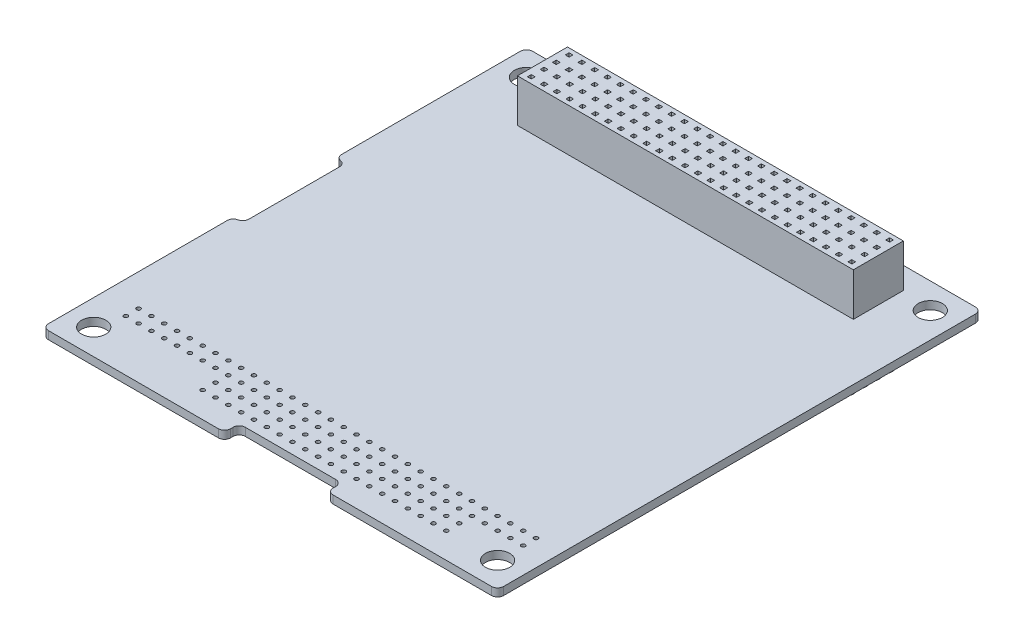
SolidWorks part; units mm, degrees
ref_plane "Front Plane" through (0, 0, 0) normal (0, 0, 1) x (1, 0, 0)
ref_plane "Top Plane" through (0, 0, 0) normal (0, 1, 0) x (1, 0, 0)
ref_plane "Right Plane" through (0, 0, 0) normal (1, 0, 0) x (0, 0, -1)
sketch "Sketch1" plane through (0, 0, 0) normal (0, 1, 0) x (1, 0, 0)
  line L1 (-45.085, -47.945) -> (45.085, -47.945)
  line L2 (-45.085, -47.945) -> (-45.085, 47.945)
  line L3 (-45.085, 47.945) -> (45.085, 47.945)
  line L4 (45.085, -47.945) -> (45.085, 47.945)
  line L5 (-45.085, -47.945) -> (45.085, 47.945) construction
  line L6 (-45.085, 47.945) -> (45.085, -47.945) construction
  point P0 (0, 0)
  dimension "D1" = 95.89
  dimension "D2" = 90.17
extrude "Boss-Extrude1" add sketch "Sketch1" along normal blind 1.57
sketch "Sketch2" plane through (0, 1.57, 0) normal (0, 1, 0) x (1, 0, 0)
  line L0 (-45.085, 47.945) -> (-9.015, 47.945) construction
  line L1 (45.085, 47.945) -> (-45.085, 47.945) construction
  line L2 (-45.085, -47.945) -> (-45.085, -10.135) construction
  line L3 (-9.015, 47.945) -> (11.305, 47.945)
  line L4 (-9.015, 47.945) -> (-9.015, 45.015)
  line L5 (-9.015, 45.015) -> (11.305, 45.015)
  line L6 (11.305, 47.945) -> (11.305, 45.015)
  line L7 (-45.085, 47.945) -> (-45.085, -47.945) construction
  line L8 (-45.085, -47.945) -> (-9.015, -47.945) construction
  line L9 (-45.085, -10.135) -> (-43.165, -10.135)
  line L10 (-45.085, -10.135) -> (-45.085, 10.135)
  line L11 (-45.085, 10.135) -> (-43.165, 10.135)
  line L12 (-43.165, -10.135) -> (-43.165, 10.135)
  line L13 (-45.085, -47.945) -> (45.085, -47.945) construction
  line L15 (-9.015, -47.945) -> (11.305, -47.945)
  line L16 (-9.015, -47.945) -> (-9.015, -45.025)
  line L17 (-9.015, -45.025) -> (11.305, -45.025)
  line L18 (11.305, -47.945) -> (11.305, -45.025)
  dimension "D1" = 36.07
  dimension "D2" = 20.32
  dimension "D3" = 2.93
  dimension "D4" = 37.81
  dimension "D5" = 20.27
  dimension "D6" = 1.92
  dimension "D7" = 2.92
extrude "Cut-Extrude1" cut sketch "Sketch2" against normal blind 1.57
sketch "Sketch3" plane through (0, 1.57, 0) normal (0, 1, 0) x (1, 0, 0)
  line L0 (-45.085, -47.945) -> (-40.005, -47.945) construction
  line L1 (-45.085, -47.945) -> (-9.015, -47.945) construction
  line L2 (-40.005, -47.945) -> (-40.005, -42.865) construction
  line L3 (45.085, -47.945) -> (40.005, -47.945) construction
  line L4 (11.305, -47.945) -> (45.085, -47.945) construction
  line L5 (40.005, -47.945) -> (40.005, -42.865) construction
  line L6 (-45.085, 47.945) -> (-40.005, 47.945) construction
  line L7 (-9.015, 47.945) -> (-45.085, 47.945) construction
  line L8 (-40.005, 47.945) -> (-40.005, 42.865) construction
  circle A0 centre (-40.005, -42.865) radius 2.4
  circle A1 centre (40.005, -42.865) radius 2.4
  circle A2 centre (-40.005, 42.865) radius 2.4
  circle A3 centre (40.005, 42.865) radius 2.4
  dimension "D3" = 4.8
  dimension "D6" = 5.08
  dimension "D4" = 5.08
  dimension "D5" = 4.8
  dimension "D7" = 4.8
  dimension "D8" = 4.8
  dimension "D1" = 5.08
  dimension "D2" = 5.08
extrude "Cut-Extrude2" cut sketch "Sketch3" against normal blind 1.57
sketch "Sketch4" plane through (0, 1.57, 0) normal (0, 1, 0) x (1, 0, 0)
  line L0 (-45.085, 47.945) -> (-45.085, 35.245) construction
  line L1 (-45.085, 47.945) -> (-45.085, 10.135) construction
  line L2 (-45.085, 35.245) -> (-31.115, 35.245) construction
  line L3 (-31.115, 35.245) -> (-32.639, 35.245)
  line L4 (-32.639, 35.245) -> (-32.639, 33.721) construction
  line L6 (-32.639, 33.721) -> (33.909, 33.721)
  line L7 (-32.639, 33.721) -> (-32.639, 43.627)
  line L8 (-32.639, 43.627) -> (33.909, 43.627)
  line L9 (33.909, 33.721) -> (33.909, 43.627)
  dimension "D1" = 12.7
  dimension "D2" = 13.97
  dimension "D3" = 1.524
  dimension "D4" = 1.524
  dimension "D5" = 9.906
  dimension "D6" = 66.548
extrude "Boss-Extrude3" add sketch "Sketch4" along normal blind 8.509 contours L6 L9 L8 L7 region at (0.635, 1.57, -38.674)
fillet "Fillet7" radius 1.2 1 edges at (-9.015, 0.785, 45.025)
fillet "Fillet8" radius 1.2 1 edges at (-9.015, 0.785, 47.945)
fillet "Fillet9" radius 1.2 2 edges at (11.305, 0.785, 47.945) (11.305, 0.785, 45.025)
fillet "Fillet10" radius 1.2 1 edges at (45.085, 0.785, 47.945)
fillet "Fillet11" radius 1.2 1 edges at (45.085, 0.785, -47.945)
fillet "Fillet12" radius 1.2 2 edges at (11.305, 0.785, -45.015) (11.305, 0.785, -47.945)
fillet "Fillet13" radius 1.2 2 edges at (-9.015, 0.785, -47.945) (-9.015, 0.785, -45.015)
fillet "Fillet14" radius 1.2 1 edges at (-45.085, 0.785, -47.945)
fillet "Fillet17" radius 1.2 1 edges at (-45.085, 0.785, -10.135)
fillet "Fillet18" radius 1.2 1 edges at (-43.165, 0.785, -10.135)
fillet "Fillet19" radius 1.2 1 edges at (-45.085, 0.785, 10.135)
fillet "Fillet20" radius 1.2 1 edges at (-43.165, 0.785, 10.135)
fillet "Fillet21" radius 1.2 1 edges at (-45.085, 0.785, 47.945)
sketch "Sketch7" plane through (0, 10.079, 0) normal (0, 1, 0) x (1, 0, 0)
  line L0 (-32.639, 33.721) -> (-31.115, 33.721) construction
  line L1 (-32.639, 33.721) -> (33.909, 33.721) construction
  line L2 (-31.115, 33.721) -> (-31.115, 34.9275) construction
  line L3 (-28.956, 34.5465) -> (-28.194, 34.5465)
  line L4 (-31.496, 34.5465) -> (-30.734, 34.5465)
  line L5 (-31.496, 34.5465) -> (-31.496, 35.3085)
  line L6 (-31.496, 35.3085) -> (-30.734, 35.3085)
  line L7 (-30.734, 34.5465) -> (-30.734, 35.3085)
  line L8 (-31.496, 34.5465) -> (-30.734, 35.3085) construction
  line L9 (-31.496, 35.3085) -> (-30.734, 34.5465) construction
  line L10 (-28.194, 34.5465) -> (-28.194, 35.3085)
  line L11 (-28.956, 35.3085) -> (-28.194, 35.3085)
  line L12 (-28.956, 34.5465) -> (-28.956, 35.3085)
  line L13 (-26.416, 34.5465) -> (-25.654, 34.5465)
  line L14 (-25.654, 34.5465) -> (-25.654, 35.3085)
  line L15 (-26.416, 35.3085) -> (-25.654, 35.3085)
  line L16 (-26.416, 34.5465) -> (-26.416, 35.3085)
  line L17 (-23.876, 34.5465) -> (-23.114, 34.5465)
  line L18 (-23.114, 34.5465) -> (-23.114, 35.3085)
  line L19 (-23.876, 35.3085) -> (-23.114, 35.3085)
  line L20 (-23.876, 34.5465) -> (-23.876, 35.3085)
  line L21 (-21.336, 34.5465) -> (-20.574, 34.5465)
  line L22 (-20.574, 34.5465) -> (-20.574, 35.3085)
  line L23 (-21.336, 35.3085) -> (-20.574, 35.3085)
  line L24 (-21.336, 34.5465) -> (-21.336, 35.3085)
  line L25 (-18.796, 34.5465) -> (-18.034, 34.5465)
  line L26 (-18.034, 34.5465) -> (-18.034, 35.3085)
  line L27 (-18.796, 35.3085) -> (-18.034, 35.3085)
  line L28 (-18.796, 34.5465) -> (-18.796, 35.3085)
  line L29 (-16.256, 34.5465) -> (-15.494, 34.5465)
  line L30 (-15.494, 34.5465) -> (-15.494, 35.3085)
  line L31 (-16.256, 35.3085) -> (-15.494, 35.3085)
  line L32 (-16.256, 34.5465) -> (-16.256, 35.3085)
  line L33 (-13.716, 34.5465) -> (-12.954, 34.5465)
  line L34 (-12.954, 34.5465) -> (-12.954, 35.3085)
  line L35 (-13.716, 35.3085) -> (-12.954, 35.3085)
  line L36 (-13.716, 34.5465) -> (-13.716, 35.3085)
  line L37 (-11.176, 34.5465) -> (-10.414, 34.5465)
  line L38 (-10.414, 34.5465) -> (-10.414, 35.3085)
  line L39 (-11.176, 35.3085) -> (-10.414, 35.3085)
  line L40 (-11.176, 34.5465) -> (-11.176, 35.3085)
  line L41 (-8.636, 34.5465) -> (-7.874, 34.5465)
  line L42 (-7.874, 34.5465) -> (-7.874, 35.3085)
  line L43 (-8.636, 35.3085) -> (-7.874, 35.3085)
  line L44 (-8.636, 34.5465) -> (-8.636, 35.3085)
  line L45 (-6.096, 34.5465) -> (-5.334, 34.5465)
  line L46 (-5.334, 34.5465) -> (-5.334, 35.3085)
  line L47 (-6.096, 35.3085) -> (-5.334, 35.3085)
  line L48 (-6.096, 34.5465) -> (-6.096, 35.3085)
  line L49 (-3.556, 34.5465) -> (-2.794, 34.5465)
  line L50 (-2.794, 34.5465) -> (-2.794, 35.3085)
  line L51 (-3.556, 35.3085) -> (-2.794, 35.3085)
  line L52 (-3.556, 34.5465) -> (-3.556, 35.3085)
  line L53 (-1.016, 34.5465) -> (-0.254, 34.5465)
  line L54 (-0.254, 34.5465) -> (-0.254, 35.3085)
  line L55 (-1.016, 35.3085) -> (-0.254, 35.3085)
  line L56 (-1.016, 34.5465) -> (-1.016, 35.3085)
  line L57 (1.524, 34.5465) -> (2.286, 34.5465)
  line L58 (2.286, 34.5465) -> (2.286, 35.3085)
  line L59 (1.524, 35.3085) -> (2.286, 35.3085)
  line L60 (1.524, 34.5465) -> (1.524, 35.3085)
  line L61 (4.064, 34.5465) -> (4.826, 34.5465)
  line L62 (4.826, 34.5465) -> (4.826, 35.3085)
  line L63 (4.064, 35.3085) -> (4.826, 35.3085)
  line L64 (4.064, 34.5465) -> (4.064, 35.3085)
  line L65 (6.604, 34.5465) -> (7.366, 34.5465)
  line L66 (7.366, 34.5465) -> (7.366, 35.3085)
  line L67 (6.604, 35.3085) -> (7.366, 35.3085)
  line L68 (6.604, 34.5465) -> (6.604, 35.3085)
  line L69 (9.144, 34.5465) -> (9.906, 34.5465)
  line L70 (9.906, 34.5465) -> (9.906, 35.3085)
  line L71 (9.144, 35.3085) -> (9.906, 35.3085)
  line L72 (9.144, 34.5465) -> (9.144, 35.3085)
  line L73 (11.684, 34.5465) -> (12.446, 34.5465)
  line L74 (12.446, 34.5465) -> (12.446, 35.3085)
  line L75 (11.684, 35.3085) -> (12.446, 35.3085)
  line L76 (11.684, 34.5465) -> (11.684, 35.3085)
  line L77 (14.224, 34.5465) -> (14.986, 34.5465)
  line L78 (14.986, 34.5465) -> (14.986, 35.3085)
  line L79 (14.224, 35.3085) -> (14.986, 35.3085)
  line L80 (14.224, 34.5465) -> (14.224, 35.3085)
  line L81 (16.764, 34.5465) -> (17.526, 34.5465)
  line L82 (17.526, 34.5465) -> (17.526, 35.3085)
  line L83 (16.764, 35.3085) -> (17.526, 35.3085)
  line L84 (16.764, 34.5465) -> (16.764, 35.3085)
  line L85 (19.304, 34.5465) -> (20.066, 34.5465)
  line L86 (20.066, 34.5465) -> (20.066, 35.3085)
  line L87 (19.304, 35.3085) -> (20.066, 35.3085)
  line L88 (19.304, 34.5465) -> (19.304, 35.3085)
  line L89 (21.844, 34.5465) -> (22.606, 34.5465)
  line L90 (22.606, 34.5465) -> (22.606, 35.3085)
  line L91 (21.844, 35.3085) -> (22.606, 35.3085)
  line L92 (21.844, 34.5465) -> (21.844, 35.3085)
  line L93 (24.384, 34.5465) -> (25.146, 34.5465)
  line L94 (25.146, 34.5465) -> (25.146, 35.3085)
  line L95 (24.384, 35.3085) -> (25.146, 35.3085)
  line L96 (24.384, 34.5465) -> (24.384, 35.3085)
  line L97 (26.924, 34.5465) -> (27.686, 34.5465)
  line L98 (27.686, 34.5465) -> (27.686, 35.3085)
  line L99 (26.924, 35.3085) -> (27.686, 35.3085)
  line L100 (26.924, 34.5465) -> (26.924, 35.3085)
  line L101 (29.464, 34.5465) -> (30.226, 34.5465)
  line L102 (30.226, 34.5465) -> (30.226, 35.3085)
  line L103 (29.464, 35.3085) -> (30.226, 35.3085)
  line L104 (29.464, 34.5465) -> (29.464, 35.3085)
  line L105 (32.004, 34.5465) -> (32.766, 34.5465)
  line L106 (32.766, 34.5465) -> (32.766, 35.3085)
  line L107 (32.004, 35.3085) -> (32.766, 35.3085)
  line L108 (32.004, 34.5465) -> (32.004, 35.3085)
  dimension "D1" = 1.524
  dimension "D2" = 1.2065
  dimension "D3" = 0.762
  dimension "D4" = 0.762
  dimension "D5" = 26
extrude "Cut-Extrude4" cut sketch "Sketch7" against normal blind 8.509
sketch "Sketch8" plane through (0, 10.079, 0) normal (0, 1, 0) x (1, 0, 0)
  line L0 (-31.496, 35.3085) -> (-30.734, 34.5465) construction
  line L1 (-31.496, 34.5465) -> (-30.734, 35.3085) construction
  line L2 (-31.115, 34.9275) -> (-31.115, 37.4675) construction
  line L3 (-28.194, 37.0865) -> (-28.956, 37.0865)
  line L4 (-30.734, 37.8485) -> (-31.496, 37.8485)
  line L5 (-30.734, 37.8485) -> (-30.734, 37.0865)
  line L6 (-30.734, 37.0865) -> (-31.496, 37.0865)
  line L7 (-31.496, 37.8485) -> (-31.496, 37.0865)
  line L8 (-30.734, 37.8485) -> (-31.496, 37.0865) construction
  line L9 (-30.734, 37.0865) -> (-31.496, 37.8485) construction
  line L10 (-28.956, 37.8485) -> (-28.956, 37.0865)
  line L11 (-28.194, 37.8485) -> (-28.956, 37.8485)
  line L12 (-28.194, 37.8485) -> (-28.194, 37.0865)
  line L13 (-25.654, 37.0865) -> (-26.416, 37.0865)
  line L14 (-26.416, 37.8485) -> (-26.416, 37.0865)
  line L15 (-25.654, 37.8485) -> (-26.416, 37.8485)
  line L16 (-25.654, 37.8485) -> (-25.654, 37.0865)
  line L17 (-23.114, 37.0865) -> (-23.876, 37.0865)
  line L18 (-23.876, 37.8485) -> (-23.876, 37.0865)
  line L19 (-23.114, 37.8485) -> (-23.876, 37.8485)
  line L20 (-23.114, 37.8485) -> (-23.114, 37.0865)
  line L21 (-20.574, 37.0865) -> (-21.336, 37.0865)
  line L22 (-21.336, 37.8485) -> (-21.336, 37.0865)
  line L23 (-20.574, 37.8485) -> (-21.336, 37.8485)
  line L24 (-20.574, 37.8485) -> (-20.574, 37.0865)
  line L25 (-18.034, 37.0865) -> (-18.796, 37.0865)
  line L26 (-18.796, 37.8485) -> (-18.796, 37.0865)
  line L27 (-18.034, 37.8485) -> (-18.796, 37.8485)
  line L28 (-18.034, 37.8485) -> (-18.034, 37.0865)
  line L29 (-15.494, 37.0865) -> (-16.256, 37.0865)
  line L30 (-16.256, 37.8485) -> (-16.256, 37.0865)
  line L31 (-15.494, 37.8485) -> (-16.256, 37.8485)
  line L32 (-15.494, 37.8485) -> (-15.494, 37.0865)
  line L33 (-12.954, 37.0865) -> (-13.716, 37.0865)
  line L34 (-13.716, 37.8485) -> (-13.716, 37.0865)
  line L35 (-12.954, 37.8485) -> (-13.716, 37.8485)
  line L36 (-12.954, 37.8485) -> (-12.954, 37.0865)
  line L37 (-10.414, 37.0865) -> (-11.176, 37.0865)
  line L38 (-11.176, 37.8485) -> (-11.176, 37.0865)
  line L39 (-10.414, 37.8485) -> (-11.176, 37.8485)
  line L40 (-10.414, 37.8485) -> (-10.414, 37.0865)
  line L41 (-7.874, 37.0865) -> (-8.636, 37.0865)
  line L42 (-8.636, 37.8485) -> (-8.636, 37.0865)
  line L43 (-7.874, 37.8485) -> (-8.636, 37.8485)
  line L44 (-7.874, 37.8485) -> (-7.874, 37.0865)
  line L45 (-5.334, 37.0865) -> (-6.096, 37.0865)
  line L46 (-6.096, 37.8485) -> (-6.096, 37.0865)
  line L47 (-5.334, 37.8485) -> (-6.096, 37.8485)
  line L48 (-5.334, 37.8485) -> (-5.334, 37.0865)
  line L49 (-2.794, 37.0865) -> (-3.556, 37.0865)
  line L50 (-3.556, 37.8485) -> (-3.556, 37.0865)
  line L51 (-2.794, 37.8485) -> (-3.556, 37.8485)
  line L52 (-2.794, 37.8485) -> (-2.794, 37.0865)
  line L53 (-0.254, 37.0865) -> (-1.016, 37.0865)
  line L54 (-1.016, 37.8485) -> (-1.016, 37.0865)
  line L55 (-0.254, 37.8485) -> (-1.016, 37.8485)
  line L56 (-0.254, 37.8485) -> (-0.254, 37.0865)
  line L57 (2.286, 37.0865) -> (1.524, 37.0865)
  line L58 (1.524, 37.8485) -> (1.524, 37.0865)
  line L59 (2.286, 37.8485) -> (1.524, 37.8485)
  line L60 (2.286, 37.8485) -> (2.286, 37.0865)
  line L61 (4.826, 37.0865) -> (4.064, 37.0865)
  line L62 (4.064, 37.8485) -> (4.064, 37.0865)
  line L63 (4.826, 37.8485) -> (4.064, 37.8485)
  line L64 (4.826, 37.8485) -> (4.826, 37.0865)
  line L65 (7.366, 37.0865) -> (6.604, 37.0865)
  line L66 (6.604, 37.8485) -> (6.604, 37.0865)
  line L67 (7.366, 37.8485) -> (6.604, 37.8485)
  line L68 (7.366, 37.8485) -> (7.366, 37.0865)
  line L69 (9.906, 37.0865) -> (9.144, 37.0865)
  line L70 (9.144, 37.8485) -> (9.144, 37.0865)
  line L71 (9.906, 37.8485) -> (9.144, 37.8485)
  line L72 (9.906, 37.8485) -> (9.906, 37.0865)
  line L73 (12.446, 37.0865) -> (11.684, 37.0865)
  line L74 (11.684, 37.8485) -> (11.684, 37.0865)
  line L75 (12.446, 37.8485) -> (11.684, 37.8485)
  line L76 (12.446, 37.8485) -> (12.446, 37.0865)
  line L77 (14.986, 37.0865) -> (14.224, 37.0865)
  line L78 (14.224, 37.8485) -> (14.224, 37.0865)
  line L79 (14.986, 37.8485) -> (14.224, 37.8485)
  line L80 (14.986, 37.8485) -> (14.986, 37.0865)
  line L81 (17.526, 37.0865) -> (16.764, 37.0865)
  line L82 (16.764, 37.8485) -> (16.764, 37.0865)
  line L83 (17.526, 37.8485) -> (16.764, 37.8485)
  line L84 (17.526, 37.8485) -> (17.526, 37.0865)
  line L85 (20.066, 37.0865) -> (19.304, 37.0865)
  line L86 (19.304, 37.8485) -> (19.304, 37.0865)
  line L87 (20.066, 37.8485) -> (19.304, 37.8485)
  line L88 (20.066, 37.8485) -> (20.066, 37.0865)
  line L89 (22.606, 37.0865) -> (21.844, 37.0865)
  line L90 (21.844, 37.8485) -> (21.844, 37.0865)
  line L91 (22.606, 37.8485) -> (21.844, 37.8485)
  line L92 (22.606, 37.8485) -> (22.606, 37.0865)
  line L93 (25.146, 37.0865) -> (24.384, 37.0865)
  line L94 (24.384, 37.8485) -> (24.384, 37.0865)
  line L95 (25.146, 37.8485) -> (24.384, 37.8485)
  line L96 (25.146, 37.8485) -> (25.146, 37.0865)
  line L97 (27.686, 37.0865) -> (26.924, 37.0865)
  line L98 (26.924, 37.8485) -> (26.924, 37.0865)
  line L99 (27.686, 37.8485) -> (26.924, 37.8485)
  line L100 (27.686, 37.8485) -> (27.686, 37.0865)
  line L101 (30.226, 37.0865) -> (29.464, 37.0865)
  line L102 (29.464, 37.8485) -> (29.464, 37.0865)
  line L103 (30.226, 37.8485) -> (29.464, 37.8485)
  line L104 (30.226, 37.8485) -> (30.226, 37.0865)
  line L105 (32.766, 37.0865) -> (32.004, 37.0865)
  line L106 (32.004, 37.8485) -> (32.004, 37.0865)
  line L107 (32.766, 37.8485) -> (32.004, 37.8485)
  line L108 (32.766, 37.8485) -> (32.766, 37.0865)
  dimension "D1" = 2.54
  dimension "D2" = 0.762
  dimension "D3" = 26
extrude "Cut-Extrude5" cut sketch "Sketch8" against normal blind 8.509
sketch "Sketch9" plane through (0, 10.079, 0) normal (0, 1, 0) x (1, 0, 0)
  line L0 (-31.496, 37.0865) -> (-30.734, 37.8485) construction
  line L1 (-30.734, 37.8485) -> (-30.734, 37.0865) construction
  line L2 (-30.734, 37.0865) -> (-31.496, 37.8485) construction
  line L3 (-31.496, 37.8485) -> (-31.115, 37.4675) construction
  line L4 (-31.115, 37.4675) -> (-31.115, 39.8805) construction
  line L5 (-28.956, 39.4995) -> (-28.194, 39.4995)
  line L6 (-31.496, 39.4995) -> (-30.734, 39.4995)
  line L7 (-31.496, 39.4995) -> (-31.496, 40.2615)
  line L8 (-31.496, 40.2615) -> (-30.734, 40.2615)
  line L9 (-30.734, 39.4995) -> (-30.734, 40.2615)
  line L10 (-31.496, 39.4995) -> (-30.734, 40.2615) construction
  line L11 (-31.496, 40.2615) -> (-30.734, 39.4995) construction
  line L12 (-28.194, 39.4995) -> (-28.194, 40.2615)
  line L13 (-28.956, 40.2615) -> (-28.194, 40.2615)
  line L14 (-28.956, 39.4995) -> (-28.956, 40.2615)
  line L15 (-26.416, 39.4995) -> (-25.654, 39.4995)
  line L16 (-25.654, 39.4995) -> (-25.654, 40.2615)
  line L17 (-26.416, 40.2615) -> (-25.654, 40.2615)
  line L18 (-26.416, 39.4995) -> (-26.416, 40.2615)
  line L19 (-23.876, 39.4995) -> (-23.114, 39.4995)
  line L20 (-23.114, 39.4995) -> (-23.114, 40.2615)
  line L21 (-23.876, 40.2615) -> (-23.114, 40.2615)
  line L22 (-23.876, 39.4995) -> (-23.876, 40.2615)
  line L23 (-21.336, 39.4995) -> (-20.574, 39.4995)
  line L24 (-20.574, 39.4995) -> (-20.574, 40.2615)
  line L25 (-21.336, 40.2615) -> (-20.574, 40.2615)
  line L26 (-21.336, 39.4995) -> (-21.336, 40.2615)
  line L27 (-18.796, 39.4995) -> (-18.034, 39.4995)
  line L28 (-18.034, 39.4995) -> (-18.034, 40.2615)
  line L29 (-18.796, 40.2615) -> (-18.034, 40.2615)
  line L30 (-18.796, 39.4995) -> (-18.796, 40.2615)
  line L31 (-16.256, 39.4995) -> (-15.494, 39.4995)
  line L32 (-15.494, 39.4995) -> (-15.494, 40.2615)
  line L33 (-16.256, 40.2615) -> (-15.494, 40.2615)
  line L34 (-16.256, 39.4995) -> (-16.256, 40.2615)
  line L35 (-13.716, 39.4995) -> (-12.954, 39.4995)
  line L36 (-12.954, 39.4995) -> (-12.954, 40.2615)
  line L37 (-13.716, 40.2615) -> (-12.954, 40.2615)
  line L38 (-13.716, 39.4995) -> (-13.716, 40.2615)
  line L39 (-11.176, 39.4995) -> (-10.414, 39.4995)
  line L40 (-10.414, 39.4995) -> (-10.414, 40.2615)
  line L41 (-11.176, 40.2615) -> (-10.414, 40.2615)
  line L42 (-11.176, 39.4995) -> (-11.176, 40.2615)
  line L43 (-8.636, 39.4995) -> (-7.874, 39.4995)
  line L44 (-7.874, 39.4995) -> (-7.874, 40.2615)
  line L45 (-8.636, 40.2615) -> (-7.874, 40.2615)
  line L46 (-8.636, 39.4995) -> (-8.636, 40.2615)
  line L47 (-6.096, 39.4995) -> (-5.334, 39.4995)
  line L48 (-5.334, 39.4995) -> (-5.334, 40.2615)
  line L49 (-6.096, 40.2615) -> (-5.334, 40.2615)
  line L50 (-6.096, 39.4995) -> (-6.096, 40.2615)
  line L51 (-3.556, 39.4995) -> (-2.794, 39.4995)
  line L52 (-2.794, 39.4995) -> (-2.794, 40.2615)
  line L53 (-3.556, 40.2615) -> (-2.794, 40.2615)
  line L54 (-3.556, 39.4995) -> (-3.556, 40.2615)
  line L55 (-1.016, 39.4995) -> (-0.254, 39.4995)
  line L56 (-0.254, 39.4995) -> (-0.254, 40.2615)
  line L57 (-1.016, 40.2615) -> (-0.254, 40.2615)
  line L58 (-1.016, 39.4995) -> (-1.016, 40.2615)
  line L59 (1.524, 39.4995) -> (2.286, 39.4995)
  line L60 (2.286, 39.4995) -> (2.286, 40.2615)
  line L61 (1.524, 40.2615) -> (2.286, 40.2615)
  line L62 (1.524, 39.4995) -> (1.524, 40.2615)
  line L63 (4.064, 39.4995) -> (4.826, 39.4995)
  line L64 (4.826, 39.4995) -> (4.826, 40.2615)
  line L65 (4.064, 40.2615) -> (4.826, 40.2615)
  line L66 (4.064, 39.4995) -> (4.064, 40.2615)
  line L67 (6.604, 39.4995) -> (7.366, 39.4995)
  line L68 (7.366, 39.4995) -> (7.366, 40.2615)
  line L69 (6.604, 40.2615) -> (7.366, 40.2615)
  line L70 (6.604, 39.4995) -> (6.604, 40.2615)
  line L71 (9.144, 39.4995) -> (9.906, 39.4995)
  line L72 (9.906, 39.4995) -> (9.906, 40.2615)
  line L73 (9.144, 40.2615) -> (9.906, 40.2615)
  line L74 (9.144, 39.4995) -> (9.144, 40.2615)
  line L75 (11.684, 39.4995) -> (12.446, 39.4995)
  line L76 (12.446, 39.4995) -> (12.446, 40.2615)
  line L77 (11.684, 40.2615) -> (12.446, 40.2615)
  line L78 (11.684, 39.4995) -> (11.684, 40.2615)
  line L79 (14.224, 39.4995) -> (14.986, 39.4995)
  line L80 (14.986, 39.4995) -> (14.986, 40.2615)
  line L81 (14.224, 40.2615) -> (14.986, 40.2615)
  line L82 (14.224, 39.4995) -> (14.224, 40.2615)
  line L83 (16.764, 39.4995) -> (17.526, 39.4995)
  line L84 (17.526, 39.4995) -> (17.526, 40.2615)
  line L85 (16.764, 40.2615) -> (17.526, 40.2615)
  line L86 (16.764, 39.4995) -> (16.764, 40.2615)
  line L87 (19.304, 39.4995) -> (20.066, 39.4995)
  line L88 (20.066, 39.4995) -> (20.066, 40.2615)
  line L89 (19.304, 40.2615) -> (20.066, 40.2615)
  line L90 (19.304, 39.4995) -> (19.304, 40.2615)
  line L91 (21.844, 39.4995) -> (22.606, 39.4995)
  line L92 (22.606, 39.4995) -> (22.606, 40.2615)
  line L93 (21.844, 40.2615) -> (22.606, 40.2615)
  line L94 (21.844, 39.4995) -> (21.844, 40.2615)
  line L95 (24.384, 39.4995) -> (25.146, 39.4995)
  line L96 (25.146, 39.4995) -> (25.146, 40.2615)
  line L97 (24.384, 40.2615) -> (25.146, 40.2615)
  line L98 (24.384, 39.4995) -> (24.384, 40.2615)
  line L99 (26.924, 39.4995) -> (27.686, 39.4995)
  line L100 (27.686, 39.4995) -> (27.686, 40.2615)
  line L101 (26.924, 40.2615) -> (27.686, 40.2615)
  line L102 (26.924, 39.4995) -> (26.924, 40.2615)
  line L103 (29.464, 39.4995) -> (30.226, 39.4995)
  line L104 (30.226, 39.4995) -> (30.226, 40.2615)
  line L105 (29.464, 40.2615) -> (30.226, 40.2615)
  line L106 (29.464, 39.4995) -> (29.464, 40.2615)
  line L107 (32.004, 39.4995) -> (32.766, 39.4995)
  line L108 (32.766, 39.4995) -> (32.766, 40.2615)
  line L109 (32.004, 40.2615) -> (32.766, 40.2615)
  line L110 (32.004, 39.4995) -> (32.004, 40.2615)
  dimension "D1" = 2.413
  dimension "D2" = 0.762
  dimension "D3" = 0.762
  dimension "D4" = 26
extrude "Cut-Extrude6" cut sketch "Sketch9" against normal blind 8.509
sketch "Sketch10" plane through (0, 10.079, 0) normal (0, 1, 0) x (1, 0, 0)
  line L0 (-30.734, 39.4995) -> (-31.496, 40.2615) construction
  line L1 (-31.496, 40.2615) -> (-31.496, 39.4995) construction
  line L2 (-31.496, 39.4995) -> (-30.734, 40.2615) construction
  line L3 (-30.734, 40.2615) -> (-31.115, 39.8805) construction
  line L4 (-31.115, 39.8805) -> (-31.115, 42.4205) construction
  line L5 (-28.194, 42.0395) -> (-28.194, 42.8015)
  line L6 (-31.496, 42.0395) -> (-30.734, 42.0395)
  line L7 (-31.496, 42.0395) -> (-31.496, 42.8015)
  line L8 (-31.496, 42.8015) -> (-30.734, 42.8015)
  line L9 (-30.734, 42.0395) -> (-30.734, 42.8015)
  line L10 (-31.496, 42.0395) -> (-30.734, 42.8015) construction
  line L11 (-31.496, 42.8015) -> (-30.734, 42.0395) construction
  line L12 (-28.956, 42.8015) -> (-28.194, 42.8015)
  line L13 (-28.956, 42.0395) -> (-28.956, 42.8015)
  line L14 (-28.956, 42.0395) -> (-28.194, 42.0395)
  line L15 (-25.654, 42.0395) -> (-25.654, 42.8015)
  line L16 (-26.416, 42.8015) -> (-25.654, 42.8015)
  line L17 (-26.416, 42.0395) -> (-26.416, 42.8015)
  line L18 (-26.416, 42.0395) -> (-25.654, 42.0395)
  line L19 (-23.114, 42.0395) -> (-23.114, 42.8015)
  line L20 (-23.876, 42.8015) -> (-23.114, 42.8015)
  line L21 (-23.876, 42.0395) -> (-23.876, 42.8015)
  line L22 (-23.876, 42.0395) -> (-23.114, 42.0395)
  line L23 (-20.574, 42.0395) -> (-20.574, 42.8015)
  line L24 (-21.336, 42.8015) -> (-20.574, 42.8015)
  line L25 (-21.336, 42.0395) -> (-21.336, 42.8015)
  line L26 (-21.336, 42.0395) -> (-20.574, 42.0395)
  line L27 (-18.034, 42.0395) -> (-18.034, 42.8015)
  line L28 (-18.796, 42.8015) -> (-18.034, 42.8015)
  line L29 (-18.796, 42.0395) -> (-18.796, 42.8015)
  line L30 (-18.796, 42.0395) -> (-18.034, 42.0395)
  line L31 (-15.494, 42.0395) -> (-15.494, 42.8015)
  line L32 (-16.256, 42.8015) -> (-15.494, 42.8015)
  line L33 (-16.256, 42.0395) -> (-16.256, 42.8015)
  line L34 (-16.256, 42.0395) -> (-15.494, 42.0395)
  line L35 (-12.954, 42.0395) -> (-12.954, 42.8015)
  line L36 (-13.716, 42.8015) -> (-12.954, 42.8015)
  line L37 (-13.716, 42.0395) -> (-13.716, 42.8015)
  line L38 (-13.716, 42.0395) -> (-12.954, 42.0395)
  line L39 (-10.414, 42.0395) -> (-10.414, 42.8015)
  line L40 (-11.176, 42.8015) -> (-10.414, 42.8015)
  line L41 (-11.176, 42.0395) -> (-11.176, 42.8015)
  line L42 (-11.176, 42.0395) -> (-10.414, 42.0395)
  line L43 (-7.874, 42.0395) -> (-7.874, 42.8015)
  line L44 (-8.636, 42.8015) -> (-7.874, 42.8015)
  line L45 (-8.636, 42.0395) -> (-8.636, 42.8015)
  line L46 (-8.636, 42.0395) -> (-7.874, 42.0395)
  line L47 (-5.334, 42.0395) -> (-5.334, 42.8015)
  line L48 (-6.096, 42.8015) -> (-5.334, 42.8015)
  line L49 (-6.096, 42.0395) -> (-6.096, 42.8015)
  line L50 (-6.096, 42.0395) -> (-5.334, 42.0395)
  line L51 (-2.794, 42.0395) -> (-2.794, 42.8015)
  line L52 (-3.556, 42.8015) -> (-2.794, 42.8015)
  line L53 (-3.556, 42.0395) -> (-3.556, 42.8015)
  line L54 (-3.556, 42.0395) -> (-2.794, 42.0395)
  line L55 (-0.254, 42.0395) -> (-0.254, 42.8015)
  line L56 (-1.016, 42.8015) -> (-0.254, 42.8015)
  line L57 (-1.016, 42.0395) -> (-1.016, 42.8015)
  line L58 (-1.016, 42.0395) -> (-0.254, 42.0395)
  line L59 (2.286, 42.0395) -> (2.286, 42.8015)
  line L60 (1.524, 42.8015) -> (2.286, 42.8015)
  line L61 (1.524, 42.0395) -> (1.524, 42.8015)
  line L62 (1.524, 42.0395) -> (2.286, 42.0395)
  line L63 (4.826, 42.0395) -> (4.826, 42.8015)
  line L64 (4.064, 42.8015) -> (4.826, 42.8015)
  line L65 (4.064, 42.0395) -> (4.064, 42.8015)
  line L66 (4.064, 42.0395) -> (4.826, 42.0395)
  line L67 (7.366, 42.0395) -> (7.366, 42.8015)
  line L68 (6.604, 42.8015) -> (7.366, 42.8015)
  line L69 (6.604, 42.0395) -> (6.604, 42.8015)
  line L70 (6.604, 42.0395) -> (7.366, 42.0395)
  line L71 (9.906, 42.0395) -> (9.906, 42.8015)
  line L72 (9.144, 42.8015) -> (9.906, 42.8015)
  line L73 (9.144, 42.0395) -> (9.144, 42.8015)
  line L74 (9.144, 42.0395) -> (9.906, 42.0395)
  line L75 (12.446, 42.0395) -> (12.446, 42.8015)
  line L76 (11.684, 42.8015) -> (12.446, 42.8015)
  line L77 (11.684, 42.0395) -> (11.684, 42.8015)
  line L78 (11.684, 42.0395) -> (12.446, 42.0395)
  line L79 (14.986, 42.0395) -> (14.986, 42.8015)
  line L80 (14.224, 42.8015) -> (14.986, 42.8015)
  line L81 (14.224, 42.0395) -> (14.224, 42.8015)
  line L82 (14.224, 42.0395) -> (14.986, 42.0395)
  line L83 (17.526, 42.0395) -> (17.526, 42.8015)
  line L84 (16.764, 42.8015) -> (17.526, 42.8015)
  line L85 (16.764, 42.0395) -> (16.764, 42.8015)
  line L86 (16.764, 42.0395) -> (17.526, 42.0395)
  line L87 (20.066, 42.0395) -> (20.066, 42.8015)
  line L88 (19.304, 42.8015) -> (20.066, 42.8015)
  line L89 (19.304, 42.0395) -> (19.304, 42.8015)
  line L90 (19.304, 42.0395) -> (20.066, 42.0395)
  line L91 (22.606, 42.0395) -> (22.606, 42.8015)
  line L92 (21.844, 42.8015) -> (22.606, 42.8015)
  line L93 (21.844, 42.0395) -> (21.844, 42.8015)
  line L94 (21.844, 42.0395) -> (22.606, 42.0395)
  line L95 (25.146, 42.0395) -> (25.146, 42.8015)
  line L96 (24.384, 42.8015) -> (25.146, 42.8015)
  line L97 (24.384, 42.0395) -> (24.384, 42.8015)
  line L98 (24.384, 42.0395) -> (25.146, 42.0395)
  line L99 (27.686, 42.0395) -> (27.686, 42.8015)
  line L100 (26.924, 42.8015) -> (27.686, 42.8015)
  line L101 (26.924, 42.0395) -> (26.924, 42.8015)
  line L102 (26.924, 42.0395) -> (27.686, 42.0395)
  line L103 (30.226, 42.0395) -> (30.226, 42.8015)
  line L104 (29.464, 42.8015) -> (30.226, 42.8015)
  line L105 (29.464, 42.0395) -> (29.464, 42.8015)
  line L106 (29.464, 42.0395) -> (30.226, 42.0395)
  line L107 (32.766, 42.0395) -> (32.766, 42.8015)
  line L108 (32.004, 42.8015) -> (32.766, 42.8015)
  line L109 (32.004, 42.0395) -> (32.004, 42.8015)
  line L110 (32.004, 42.0395) -> (32.766, 42.0395)
  dimension "D1" = 2.54
  dimension "D2" = 0.762
  dimension "D3" = 0.762
  dimension "D4" = 26
extrude "Cut-Extrude7" cut sketch "Sketch10" against normal blind 8.509
sketch "Sketch11" plane through (0, 1.57, 0) normal (0, 1, 0) x (1, 0, 0)
  line L0 (-43.885, -47.945) -> (-45.2926, -47.945) construction
  line L1 (-45.085, -46.745) -> (-45.085, -47.945) construction
  line L2 (-45.085, -47.945) -> (-38.735, -47.945) construction
  line L3 (-43.885, -47.945) -> (-10.215, -47.945) construction
  line L4 (-38.735, -47.945) -> (-38.735, -37.785) construction
  circle A0 centre (-38.735, -37.785) radius 0.4
  circle A1 centre (-36.195, -37.785) radius 0.4
  circle A2 centre (-33.655, -37.785) radius 0.4
  circle A3 centre (-31.115, -37.785) radius 0.4
  circle A4 centre (-28.575, -37.785) radius 0.4
  circle A5 centre (-26.035, -37.785) radius 0.4
  circle A6 centre (-23.495, -37.785) radius 0.4
  circle A7 centre (-20.955, -37.785) radius 0.4
  circle A8 centre (-18.415, -37.785) radius 0.4
  circle A9 centre (-15.875, -37.785) radius 0.4
  circle A10 centre (-13.335, -37.785) radius 0.4
  circle A11 centre (-10.795, -37.785) radius 0.4
  circle A12 centre (-8.255, -37.785) radius 0.4
  circle A13 centre (-5.715, -37.785) radius 0.4
  circle A14 centre (-3.175, -37.785) radius 0.4
  circle A15 centre (-0.635, -37.785) radius 0.4
  circle A16 centre (1.905, -37.785) radius 0.4
  circle A17 centre (4.445, -37.785) radius 0.4
  circle A18 centre (6.985, -37.785) radius 0.4
  circle A19 centre (9.525, -37.785) radius 0.4
  circle A20 centre (12.065, -37.785) radius 0.4
  circle A21 centre (14.605, -37.785) radius 0.4
  circle A22 centre (17.145, -37.785) radius 0.4
  circle A23 centre (19.685, -37.785) radius 0.4
  circle A24 centre (22.225, -37.785) radius 0.4
  circle A25 centre (24.765, -37.785) radius 0.4
  circle A26 centre (27.305, -37.785) radius 0.4
  circle A27 centre (29.845, -37.785) radius 0.4
  circle A28 centre (32.385, -37.785) radius 0.4
  circle A29 centre (34.925, -37.785) radius 0.4
  circle A30 centre (37.465, -37.785) radius 0.4
  circle A31 centre (40.005, -37.785) radius 0.4
  dimension "D3" = 0.8
  dimension "D1" = 6.35
  dimension "D2" = 10.16
  dimension "D4" = 32
extrude "Cut-Extrude8" cut sketch "Sketch11" against normal blind 10
sketch "Sketch12" plane through (0, 1.57, 0) normal (0, 1, 0) x (1, 0, 0)
  line L0 (-38.735, -37.785) -> (-38.735, -35.245) construction
  circle A0 centre (-38.735, -35.245) radius 0.4
  circle A1 centre (-36.195, -35.245) radius 0.4
  circle A2 centre (-33.655, -35.245) radius 0.4
  circle A3 centre (-31.115, -35.245) radius 0.4
  circle A4 centre (-28.575, -35.245) radius 0.4
  circle A5 centre (-26.035, -35.245) radius 0.4
  circle A6 centre (-23.495, -35.245) radius 0.4
  circle A7 centre (-20.955, -35.245) radius 0.4
  circle A8 centre (-18.415, -35.245) radius 0.4
  circle A9 centre (-15.875, -35.245) radius 0.4
  circle A10 centre (-13.335, -35.245) radius 0.4
  circle A11 centre (-10.795, -35.245) radius 0.4
  circle A12 centre (-8.255, -35.245) radius 0.4
  circle A13 centre (-5.715, -35.245) radius 0.4
  circle A14 centre (-3.175, -35.245) radius 0.4
  circle A15 centre (-0.635, -35.245) radius 0.4
  circle A16 centre (1.905, -35.245) radius 0.4
  circle A17 centre (4.445, -35.245) radius 0.4
  circle A18 centre (6.985, -35.245) radius 0.4
  circle A19 centre (9.525, -35.245) radius 0.4
  circle A20 centre (12.065, -35.245) radius 0.4
  circle A21 centre (14.605, -35.245) radius 0.4
  circle A22 centre (17.145, -35.245) radius 0.4
  circle A23 centre (19.685, -35.245) radius 0.4
  circle A24 centre (22.225, -35.245) radius 0.4
  circle A25 centre (24.765, -35.245) radius 0.4
  circle A26 centre (27.305, -35.245) radius 0.4
  circle A27 centre (29.845, -35.245) radius 0.4
  circle A28 centre (32.385, -35.245) radius 0.4
  circle A29 centre (34.925, -35.245) radius 0.4
  circle A30 centre (37.465, -35.245) radius 0.4
  circle A31 centre (40.005, -35.245) radius 0.4
  dimension "D2" = 0.8
  dimension "D1" = 2.54
  dimension "D3" = 32
extrude "Cut-Extrude9" cut sketch "Sketch12" against normal blind 10
sketch "Sketch13" plane through (0, 1.57, 0) normal (0, 1, 0) x (1, 0, 0)
  line L0 (-43.885, -47.945) -> (-45.085, -47.945) construction
  line L1 (-45.085, -47.945) -> (-45.085, -46.745) construction
  line L2 (-45.085, -47.945) -> (-18.415, -47.945) construction
  line L3 (-43.885, -47.945) -> (-10.215, -47.945) construction
  line L4 (-18.415, -47.945) -> (-18.415, -42.865) construction
  circle A0 centre (-18.415, -42.865) radius 0.4
  circle A1 centre (-15.875, -42.865) radius 0.4
  circle A2 centre (-13.335, -42.865) radius 0.4
  circle A3 centre (-10.795, -42.865) radius 0.4
  circle A4 centre (-8.255, -42.865) radius 0.4
  circle A5 centre (-5.715, -42.865) radius 0.4
  circle A6 centre (-3.175, -42.865) radius 0.4
  circle A7 centre (-0.635, -42.865) radius 0.4
  circle A8 centre (1.905, -42.865) radius 0.4
  circle A9 centre (4.445, -42.865) radius 0.4
  circle A10 centre (6.985, -42.865) radius 0.4
  circle A11 centre (9.525, -42.865) radius 0.4
  circle A12 centre (12.065, -42.865) radius 0.4
  circle A13 centre (14.605, -42.865) radius 0.4
  circle A14 centre (17.145, -42.865) radius 0.4
  circle A15 centre (19.685, -42.865) radius 0.4
  circle A16 centre (22.225, -42.865) radius 0.4
  circle A17 centre (24.765, -42.865) radius 0.4
  circle A18 centre (27.305, -42.865) radius 0.4
  circle A19 centre (29.845, -42.865) radius 0.4
  dimension "D3" = 0.8
  dimension "D1" = 26.67
  dimension "D2" = 5.08
  dimension "D4" = 20
extrude "Cut-Extrude10" cut sketch "Sketch13" against normal blind 10
sketch "Sketch14" plane through (0, 1.57, 0) normal (0, 1, 0) x (1, 0, 0)
  line L0 (-18.415, -42.865) -> (-18.415, -40.325) construction
  circle A0 centre (-18.415, -40.325) radius 0.4
  circle A1 centre (-15.875, -40.325) radius 0.4
  circle A2 centre (-13.335, -40.325) radius 0.4
  circle A3 centre (-10.795, -40.325) radius 0.4
  circle A4 centre (-8.255, -40.325) radius 0.4
  circle A5 centre (-5.715, -40.325) radius 0.4
  circle A6 centre (-3.175, -40.325) radius 0.4
  circle A7 centre (-0.635, -40.325) radius 0.4
  circle A8 centre (1.905, -40.325) radius 0.4
  circle A9 centre (4.445, -40.325) radius 0.4
  circle A10 centre (6.985, -40.325) radius 0.4
  circle A11 centre (9.525, -40.325) radius 0.4
  circle A12 centre (12.065, -40.325) radius 0.4
  circle A13 centre (14.605, -40.325) radius 0.4
  circle A14 centre (17.145, -40.325) radius 0.4
  circle A15 centre (19.685, -40.325) radius 0.4
  circle A16 centre (22.225, -40.325) radius 0.4
  circle A17 centre (24.765, -40.325) radius 0.4
  circle A18 centre (27.305, -40.325) radius 0.4
  circle A19 centre (29.845, -40.325) radius 0.4
  dimension "D2" = 0.8
  dimension "D1" = 2.54
  dimension "D3" = 20
extrude "Cut-Extrude11" cut sketch "Sketch14" against normal blind 10
sketch "Sketch15" plane through (0, 0, 0) normal (0, -1, 0) x (1, 0, 0)
  line L0 (-28.2575, -42.738) -> (-28.2575, -42.103)
  line L1 (-31.4325, -42.738) -> (-30.7975, -42.738)
  line L2 (-31.4325, -42.738) -> (-31.4325, -42.103)
  line L3 (-28.8925, -42.738) -> (-28.2575, -42.738)
  line L4 (-31.4325, -42.103) -> (-30.7975, -42.103)
  line L5 (-28.8925, -42.103) -> (-28.2575, -42.103)
  line L6 (-31.115, -42.4205) -> (-28.575, -42.4205) construction
  line L7 (-30.7975, -42.738) -> (-30.7975, -42.103)
  line L8 (-31.4325, -42.738) -> (-30.7975, -42.103) construction
  line L9 (-31.4325, -42.103) -> (-30.7975, -42.738) construction
  line L10 (-28.8925, -42.738) -> (-28.8925, -42.103)
  line L11 (-25.7175, -42.738) -> (-25.7175, -42.103)
  line L12 (-26.3525, -42.738) -> (-25.7175, -42.738)
  line L13 (-26.3525, -42.103) -> (-25.7175, -42.103)
  line L14 (-26.3525, -42.738) -> (-26.3525, -42.103)
  line L15 (-23.1775, -42.738) -> (-23.1775, -42.103)
  line L16 (-23.8125, -42.738) -> (-23.1775, -42.738)
  line L17 (-23.8125, -42.103) -> (-23.1775, -42.103)
  line L18 (-23.8125, -42.738) -> (-23.8125, -42.103)
  line L19 (-20.6375, -42.738) -> (-20.6375, -42.103)
  line L20 (-21.2725, -42.738) -> (-20.6375, -42.738)
  line L21 (-21.2725, -42.103) -> (-20.6375, -42.103)
  line L22 (-21.2725, -42.738) -> (-21.2725, -42.103)
  line L23 (-18.0975, -42.738) -> (-18.0975, -42.103)
  line L24 (-18.7325, -42.738) -> (-18.0975, -42.738)
  line L25 (-18.7325, -42.103) -> (-18.0975, -42.103)
  line L26 (-18.7325, -42.738) -> (-18.7325, -42.103)
  line L27 (-15.5575, -42.738) -> (-15.5575, -42.103)
  line L28 (-16.1925, -42.738) -> (-15.5575, -42.738)
  line L29 (-16.1925, -42.103) -> (-15.5575, -42.103)
  line L30 (-16.1925, -42.738) -> (-16.1925, -42.103)
  line L31 (-13.0175, -42.738) -> (-13.0175, -42.103)
  line L32 (-13.6525, -42.738) -> (-13.0175, -42.738)
  line L33 (-13.6525, -42.103) -> (-13.0175, -42.103)
  line L34 (-13.6525, -42.738) -> (-13.6525, -42.103)
  line L35 (-10.4775, -42.738) -> (-10.4775, -42.103)
  line L36 (-11.1125, -42.738) -> (-10.4775, -42.738)
  line L37 (-11.1125, -42.103) -> (-10.4775, -42.103)
  line L38 (-11.1125, -42.738) -> (-11.1125, -42.103)
  line L39 (-7.9375, -42.738) -> (-7.9375, -42.103)
  line L40 (-8.5725, -42.738) -> (-7.9375, -42.738)
  line L41 (-8.5725, -42.103) -> (-7.9375, -42.103)
  line L42 (-8.5725, -42.738) -> (-8.5725, -42.103)
  line L43 (-5.3975, -42.738) -> (-5.3975, -42.103)
  line L44 (-6.0325, -42.738) -> (-5.3975, -42.738)
  line L45 (-6.0325, -42.103) -> (-5.3975, -42.103)
  line L46 (-6.0325, -42.738) -> (-6.0325, -42.103)
  line L47 (-2.8575, -42.738) -> (-2.8575, -42.103)
  line L48 (-3.4925, -42.738) -> (-2.8575, -42.738)
  line L49 (-3.4925, -42.103) -> (-2.8575, -42.103)
  line L50 (-3.4925, -42.738) -> (-3.4925, -42.103)
  line L51 (-0.3175, -42.738) -> (-0.3175, -42.103)
  line L52 (-0.9525, -42.738) -> (-0.3175, -42.738)
  line L53 (-0.9525, -42.103) -> (-0.3175, -42.103)
  line L54 (-0.9525, -42.738) -> (-0.9525, -42.103)
  line L55 (2.2225, -42.738) -> (2.2225, -42.103)
  line L56 (1.5875, -42.738) -> (2.2225, -42.738)
  line L57 (1.5875, -42.103) -> (2.2225, -42.103)
  line L58 (1.5875, -42.738) -> (1.5875, -42.103)
  line L59 (4.7625, -42.738) -> (4.7625, -42.103)
  line L60 (4.1275, -42.738) -> (4.7625, -42.738)
  line L61 (4.1275, -42.103) -> (4.7625, -42.103)
  line L62 (4.1275, -42.738) -> (4.1275, -42.103)
  line L63 (7.3025, -42.738) -> (7.3025, -42.103)
  line L64 (6.6675, -42.738) -> (7.3025, -42.738)
  line L65 (6.6675, -42.103) -> (7.3025, -42.103)
  line L66 (6.6675, -42.738) -> (6.6675, -42.103)
  line L67 (9.8425, -42.738) -> (9.8425, -42.103)
  line L68 (9.2075, -42.738) -> (9.8425, -42.738)
  line L69 (9.2075, -42.103) -> (9.8425, -42.103)
  line L70 (9.2075, -42.738) -> (9.2075, -42.103)
  line L71 (12.3825, -42.738) -> (12.3825, -42.103)
  line L72 (11.7475, -42.738) -> (12.3825, -42.738)
  line L73 (11.7475, -42.103) -> (12.3825, -42.103)
  line L74 (11.7475, -42.738) -> (11.7475, -42.103)
  line L75 (14.9225, -42.738) -> (14.9225, -42.103)
  line L76 (14.2875, -42.738) -> (14.9225, -42.738)
  line L77 (14.2875, -42.103) -> (14.9225, -42.103)
  line L78 (14.2875, -42.738) -> (14.2875, -42.103)
  line L79 (17.4625, -42.738) -> (17.4625, -42.103)
  line L80 (16.8275, -42.738) -> (17.4625, -42.738)
  line L81 (16.8275, -42.103) -> (17.4625, -42.103)
  line L82 (16.8275, -42.738) -> (16.8275, -42.103)
  line L83 (20.0025, -42.738) -> (20.0025, -42.103)
  line L84 (19.3675, -42.738) -> (20.0025, -42.738)
  line L85 (19.3675, -42.103) -> (20.0025, -42.103)
  line L86 (19.3675, -42.738) -> (19.3675, -42.103)
  line L87 (22.5425, -42.738) -> (22.5425, -42.103)
  line L88 (21.9075, -42.738) -> (22.5425, -42.738)
  line L89 (21.9075, -42.103) -> (22.5425, -42.103)
  line L90 (21.9075, -42.738) -> (21.9075, -42.103)
  line L91 (25.0825, -42.738) -> (25.0825, -42.103)
  line L92 (24.4475, -42.738) -> (25.0825, -42.738)
  line L93 (24.4475, -42.103) -> (25.0825, -42.103)
  line L94 (24.4475, -42.738) -> (24.4475, -42.103)
  line L95 (27.6225, -42.738) -> (27.6225, -42.103)
  line L96 (26.9875, -42.738) -> (27.6225, -42.738)
  line L97 (26.9875, -42.103) -> (27.6225, -42.103)
  line L98 (26.9875, -42.738) -> (26.9875, -42.103)
  line L99 (30.1625, -42.738) -> (30.1625, -42.103)
  line L100 (29.5275, -42.738) -> (30.1625, -42.738)
  line L101 (29.5275, -42.103) -> (30.1625, -42.103)
  line L102 (29.5275, -42.738) -> (29.5275, -42.103)
  line L103 (32.7025, -42.738) -> (32.7025, -42.103)
  line L104 (32.0675, -42.738) -> (32.7025, -42.738)
  line L105 (32.0675, -42.103) -> (32.7025, -42.103)
  line L106 (32.0675, -42.738) -> (32.0675, -42.103)
  dimension "D1" = 0.635
  dimension "D2" = 0.635
  dimension "D3" = 26
extrude "Boss-Extrude4" add sketch "Sketch15" along normal blind 12.446
sketch "Sketch16" plane through (0, 0, 0) normal (0, -1, 0) x (1, 0, 0)
  line L0 (-31.4325, -42.738) -> (-30.7975, -42.103) construction
  line L1 (-30.7975, -42.738) -> (-31.4325, -42.103) construction
  line L2 (-31.115, -42.4205) -> (-31.115, -39.8805) construction
  line L3 (-31.115, -39.8805) -> (-31.115, -37.3405) construction
  line L4 (-31.4325, -40.198) -> (-30.7975, -40.198)
  line L5 (-31.4325, -40.198) -> (-31.4325, -39.563)
  line L6 (-31.4325, -39.563) -> (-30.7975, -39.563)
  line L7 (-30.7975, -40.198) -> (-30.7975, -39.563)
  line L8 (-31.4325, -40.198) -> (-30.7975, -39.563) construction
  line L9 (-31.4325, -39.563) -> (-30.7975, -40.198) construction
  line L10 (-31.115, -37.3405) -> (-31.115, -34.8005) construction
  line L11 (-30.7975, -37.658) -> (-31.4325, -37.658)
  line L12 (-30.7975, -37.658) -> (-30.7975, -37.023)
  line L13 (-30.7975, -37.023) -> (-31.4325, -37.023)
  line L14 (-31.4325, -37.658) -> (-31.4325, -37.023)
  line L15 (-30.7975, -37.658) -> (-31.4325, -37.023) construction
  line L16 (-30.7975, -37.023) -> (-31.4325, -37.658) construction
  line L17 (-28.8925, -40.198) -> (-28.2575, -40.198)
  line L18 (-30.7975, -35.118) -> (-31.4325, -35.118)
  line L19 (-30.7975, -35.118) -> (-30.7975, -34.483)
  line L20 (-30.7975, -34.483) -> (-31.4325, -34.483)
  line L21 (-31.4325, -35.118) -> (-31.4325, -34.483)
  line L22 (-30.7975, -35.118) -> (-31.4325, -34.483) construction
  line L23 (-30.7975, -34.483) -> (-31.4325, -35.118) construction
  line L24 (-28.2575, -40.198) -> (-28.2575, -39.563)
  line L25 (-28.8925, -39.563) -> (-28.2575, -39.563)
  line L26 (-28.8925, -40.198) -> (-28.8925, -39.563)
  line L27 (-28.2575, -37.658) -> (-28.8925, -37.658)
  line L28 (-28.2575, -37.658) -> (-28.2575, -37.023)
  line L29 (-28.8925, -37.658) -> (-28.8925, -37.023)
  line L30 (-28.2575, -37.023) -> (-28.8925, -37.023)
  line L31 (-28.2575, -35.118) -> (-28.8925, -35.118)
  line L32 (-28.2575, -35.118) -> (-28.2575, -34.483)
  line L33 (-28.2575, -34.483) -> (-28.8925, -34.483)
  line L34 (-28.8925, -35.118) -> (-28.8925, -34.483)
  line L35 (-26.3525, -40.198) -> (-25.7175, -40.198)
  line L36 (-25.7175, -40.198) -> (-25.7175, -39.563)
  line L37 (-26.3525, -39.563) -> (-25.7175, -39.563)
  line L38 (-26.3525, -40.198) -> (-26.3525, -39.563)
  line L39 (-25.7175, -37.658) -> (-26.3525, -37.658)
  line L40 (-25.7175, -37.658) -> (-25.7175, -37.023)
  line L41 (-26.3525, -37.658) -> (-26.3525, -37.023)
  line L42 (-25.7175, -37.023) -> (-26.3525, -37.023)
  line L43 (-25.7175, -35.118) -> (-26.3525, -35.118)
  line L44 (-25.7175, -35.118) -> (-25.7175, -34.483)
  line L45 (-25.7175, -34.483) -> (-26.3525, -34.483)
  line L46 (-26.3525, -35.118) -> (-26.3525, -34.483)
  line L47 (-23.8125, -40.198) -> (-23.1775, -40.198)
  line L48 (-23.1775, -40.198) -> (-23.1775, -39.563)
  line L49 (-23.8125, -39.563) -> (-23.1775, -39.563)
  line L50 (-23.8125, -40.198) -> (-23.8125, -39.563)
  line L51 (-23.1775, -37.658) -> (-23.8125, -37.658)
  line L52 (-23.1775, -37.658) -> (-23.1775, -37.023)
  line L53 (-23.8125, -37.658) -> (-23.8125, -37.023)
  line L54 (-23.1775, -37.023) -> (-23.8125, -37.023)
  line L55 (-23.1775, -35.118) -> (-23.8125, -35.118)
  line L56 (-23.1775, -35.118) -> (-23.1775, -34.483)
  line L57 (-23.1775, -34.483) -> (-23.8125, -34.483)
  line L58 (-23.8125, -35.118) -> (-23.8125, -34.483)
  line L59 (-21.2725, -40.198) -> (-20.6375, -40.198)
  line L60 (-20.6375, -40.198) -> (-20.6375, -39.563)
  line L61 (-21.2725, -39.563) -> (-20.6375, -39.563)
  line L62 (-21.2725, -40.198) -> (-21.2725, -39.563)
  line L63 (-20.6375, -37.658) -> (-21.2725, -37.658)
  line L64 (-20.6375, -37.658) -> (-20.6375, -37.023)
  line L65 (-21.2725, -37.658) -> (-21.2725, -37.023)
  line L66 (-20.6375, -37.023) -> (-21.2725, -37.023)
  line L67 (-20.6375, -35.118) -> (-21.2725, -35.118)
  line L68 (-20.6375, -35.118) -> (-20.6375, -34.483)
  line L69 (-20.6375, -34.483) -> (-21.2725, -34.483)
  line L70 (-21.2725, -35.118) -> (-21.2725, -34.483)
  line L71 (-18.7325, -40.198) -> (-18.0975, -40.198)
  line L72 (-18.0975, -40.198) -> (-18.0975, -39.563)
  line L73 (-18.7325, -39.563) -> (-18.0975, -39.563)
  line L74 (-18.7325, -40.198) -> (-18.7325, -39.563)
  line L75 (-18.0975, -37.658) -> (-18.7325, -37.658)
  line L76 (-18.0975, -37.658) -> (-18.0975, -37.023)
  line L77 (-18.7325, -37.658) -> (-18.7325, -37.023)
  line L78 (-18.0975, -37.023) -> (-18.7325, -37.023)
  line L79 (-18.0975, -35.118) -> (-18.7325, -35.118)
  line L80 (-18.0975, -35.118) -> (-18.0975, -34.483)
  line L81 (-18.0975, -34.483) -> (-18.7325, -34.483)
  line L82 (-18.7325, -35.118) -> (-18.7325, -34.483)
  line L83 (-16.1925, -40.198) -> (-15.5575, -40.198)
  line L84 (-15.5575, -40.198) -> (-15.5575, -39.563)
  line L85 (-16.1925, -39.563) -> (-15.5575, -39.563)
  line L86 (-16.1925, -40.198) -> (-16.1925, -39.563)
  line L87 (-15.5575, -37.658) -> (-16.1925, -37.658)
  line L88 (-15.5575, -37.658) -> (-15.5575, -37.023)
  line L89 (-16.1925, -37.658) -> (-16.1925, -37.023)
  line L90 (-15.5575, -37.023) -> (-16.1925, -37.023)
  line L91 (-15.5575, -35.118) -> (-16.1925, -35.118)
  line L92 (-15.5575, -35.118) -> (-15.5575, -34.483)
  line L93 (-15.5575, -34.483) -> (-16.1925, -34.483)
  line L94 (-16.1925, -35.118) -> (-16.1925, -34.483)
  line L95 (-13.6525, -40.198) -> (-13.0175, -40.198)
  line L96 (-13.0175, -40.198) -> (-13.0175, -39.563)
  line L97 (-13.6525, -39.563) -> (-13.0175, -39.563)
  line L98 (-13.6525, -40.198) -> (-13.6525, -39.563)
  line L99 (-13.0175, -37.658) -> (-13.6525, -37.658)
  line L100 (-13.0175, -37.658) -> (-13.0175, -37.023)
  line L101 (-13.6525, -37.658) -> (-13.6525, -37.023)
  line L102 (-13.0175, -37.023) -> (-13.6525, -37.023)
  line L103 (-13.0175, -35.118) -> (-13.6525, -35.118)
  line L104 (-13.0175, -35.118) -> (-13.0175, -34.483)
  line L105 (-13.0175, -34.483) -> (-13.6525, -34.483)
  line L106 (-13.6525, -35.118) -> (-13.6525, -34.483)
  line L107 (-11.1125, -40.198) -> (-10.4775, -40.198)
  line L108 (-10.4775, -40.198) -> (-10.4775, -39.563)
  line L109 (-11.1125, -39.563) -> (-10.4775, -39.563)
  line L110 (-11.1125, -40.198) -> (-11.1125, -39.563)
  line L111 (-10.4775, -37.658) -> (-11.1125, -37.658)
  line L112 (-10.4775, -37.658) -> (-10.4775, -37.023)
  line L113 (-11.1125, -37.658) -> (-11.1125, -37.023)
  line L114 (-10.4775, -37.023) -> (-11.1125, -37.023)
  line L115 (-10.4775, -35.118) -> (-11.1125, -35.118)
  line L116 (-10.4775, -35.118) -> (-10.4775, -34.483)
  line L117 (-10.4775, -34.483) -> (-11.1125, -34.483)
  line L118 (-11.1125, -35.118) -> (-11.1125, -34.483)
  line L119 (-8.5725, -40.198) -> (-7.9375, -40.198)
  line L120 (-7.9375, -40.198) -> (-7.9375, -39.563)
  line L121 (-8.5725, -39.563) -> (-7.9375, -39.563)
  line L122 (-8.5725, -40.198) -> (-8.5725, -39.563)
  line L123 (-7.9375, -37.658) -> (-8.5725, -37.658)
  line L124 (-7.9375, -37.658) -> (-7.9375, -37.023)
  line L125 (-8.5725, -37.658) -> (-8.5725, -37.023)
  line L126 (-7.9375, -37.023) -> (-8.5725, -37.023)
  line L127 (-7.9375, -35.118) -> (-8.5725, -35.118)
  line L128 (-7.9375, -35.118) -> (-7.9375, -34.483)
  line L129 (-7.9375, -34.483) -> (-8.5725, -34.483)
  line L130 (-8.5725, -35.118) -> (-8.5725, -34.483)
  line L131 (-6.0325, -40.198) -> (-5.3975, -40.198)
  line L132 (-5.3975, -40.198) -> (-5.3975, -39.563)
  line L133 (-6.0325, -39.563) -> (-5.3975, -39.563)
  line L134 (-6.0325, -40.198) -> (-6.0325, -39.563)
  line L135 (-5.3975, -37.658) -> (-6.0325, -37.658)
  line L136 (-5.3975, -37.658) -> (-5.3975, -37.023)
  line L137 (-6.0325, -37.658) -> (-6.0325, -37.023)
  line L138 (-5.3975, -37.023) -> (-6.0325, -37.023)
  line L139 (-5.3975, -35.118) -> (-6.0325, -35.118)
  line L140 (-5.3975, -35.118) -> (-5.3975, -34.483)
  line L141 (-5.3975, -34.483) -> (-6.0325, -34.483)
  line L142 (-6.0325, -35.118) -> (-6.0325, -34.483)
  line L143 (-3.4925, -40.198) -> (-2.8575, -40.198)
  line L144 (-2.8575, -40.198) -> (-2.8575, -39.563)
  line L145 (-3.4925, -39.563) -> (-2.8575, -39.563)
  line L146 (-3.4925, -40.198) -> (-3.4925, -39.563)
  line L147 (-2.8575, -37.658) -> (-3.4925, -37.658)
  line L148 (-2.8575, -37.658) -> (-2.8575, -37.023)
  line L149 (-3.4925, -37.658) -> (-3.4925, -37.023)
  line L150 (-2.8575, -37.023) -> (-3.4925, -37.023)
  line L151 (-2.8575, -35.118) -> (-3.4925, -35.118)
  line L152 (-2.8575, -35.118) -> (-2.8575, -34.483)
  line L153 (-2.8575, -34.483) -> (-3.4925, -34.483)
  line L154 (-3.4925, -35.118) -> (-3.4925, -34.483)
  line L155 (-0.9525, -40.198) -> (-0.3175, -40.198)
  line L156 (-0.3175, -40.198) -> (-0.3175, -39.563)
  line L157 (-0.9525, -39.563) -> (-0.3175, -39.563)
  line L158 (-0.9525, -40.198) -> (-0.9525, -39.563)
  line L159 (-0.3175, -37.658) -> (-0.9525, -37.658)
  line L160 (-0.3175, -37.658) -> (-0.3175, -37.023)
  line L161 (-0.9525, -37.658) -> (-0.9525, -37.023)
  line L162 (-0.3175, -37.023) -> (-0.9525, -37.023)
  line L163 (-0.3175, -35.118) -> (-0.9525, -35.118)
  line L164 (-0.3175, -35.118) -> (-0.3175, -34.483)
  line L165 (-0.3175, -34.483) -> (-0.9525, -34.483)
  line L166 (-0.9525, -35.118) -> (-0.9525, -34.483)
  line L167 (1.5875, -40.198) -> (2.2225, -40.198)
  line L168 (2.2225, -40.198) -> (2.2225, -39.563)
  line L169 (1.5875, -39.563) -> (2.2225, -39.563)
  line L170 (1.5875, -40.198) -> (1.5875, -39.563)
  line L171 (2.2225, -37.658) -> (1.5875, -37.658)
  line L172 (2.2225, -37.658) -> (2.2225, -37.023)
  line L173 (1.5875, -37.658) -> (1.5875, -37.023)
  line L174 (2.2225, -37.023) -> (1.5875, -37.023)
  line L175 (2.2225, -35.118) -> (1.5875, -35.118)
  line L176 (2.2225, -35.118) -> (2.2225, -34.483)
  line L177 (2.2225, -34.483) -> (1.5875, -34.483)
  line L178 (1.5875, -35.118) -> (1.5875, -34.483)
  line L179 (4.1275, -40.198) -> (4.7625, -40.198)
  line L180 (4.7625, -40.198) -> (4.7625, -39.563)
  line L181 (4.1275, -39.563) -> (4.7625, -39.563)
  line L182 (4.1275, -40.198) -> (4.1275, -39.563)
  line L183 (4.7625, -37.658) -> (4.1275, -37.658)
  line L184 (4.7625, -37.658) -> (4.7625, -37.023)
  line L185 (4.1275, -37.658) -> (4.1275, -37.023)
  line L186 (4.7625, -37.023) -> (4.1275, -37.023)
  line L187 (4.7625, -35.118) -> (4.1275, -35.118)
  line L188 (4.7625, -35.118) -> (4.7625, -34.483)
  line L189 (4.7625, -34.483) -> (4.1275, -34.483)
  line L190 (4.1275, -35.118) -> (4.1275, -34.483)
  line L191 (6.6675, -40.198) -> (7.3025, -40.198)
  line L192 (7.3025, -40.198) -> (7.3025, -39.563)
  line L193 (6.6675, -39.563) -> (7.3025, -39.563)
  line L194 (6.6675, -40.198) -> (6.6675, -39.563)
  line L195 (7.3025, -37.658) -> (6.6675, -37.658)
  line L196 (7.3025, -37.658) -> (7.3025, -37.023)
  line L197 (6.6675, -37.658) -> (6.6675, -37.023)
  line L198 (7.3025, -37.023) -> (6.6675, -37.023)
  line L199 (7.3025, -35.118) -> (6.6675, -35.118)
  line L200 (7.3025, -35.118) -> (7.3025, -34.483)
  line L201 (7.3025, -34.483) -> (6.6675, -34.483)
  line L202 (6.6675, -35.118) -> (6.6675, -34.483)
  line L203 (9.2075, -40.198) -> (9.8425, -40.198)
  line L204 (9.8425, -40.198) -> (9.8425, -39.563)
  line L205 (9.2075, -39.563) -> (9.8425, -39.563)
  line L206 (9.2075, -40.198) -> (9.2075, -39.563)
  line L207 (9.8425, -37.658) -> (9.2075, -37.658)
  line L208 (9.8425, -37.658) -> (9.8425, -37.023)
  line L209 (9.2075, -37.658) -> (9.2075, -37.023)
  line L210 (9.8425, -37.023) -> (9.2075, -37.023)
  line L211 (9.8425, -35.118) -> (9.2075, -35.118)
  line L212 (9.8425, -35.118) -> (9.8425, -34.483)
  line L213 (9.8425, -34.483) -> (9.2075, -34.483)
  line L214 (9.2075, -35.118) -> (9.2075, -34.483)
  line L215 (11.7475, -40.198) -> (12.3825, -40.198)
  line L216 (12.3825, -40.198) -> (12.3825, -39.563)
  line L217 (11.7475, -39.563) -> (12.3825, -39.563)
  line L218 (11.7475, -40.198) -> (11.7475, -39.563)
  line L219 (12.3825, -37.658) -> (11.7475, -37.658)
  line L220 (12.3825, -37.658) -> (12.3825, -37.023)
  line L221 (11.7475, -37.658) -> (11.7475, -37.023)
  line L222 (12.3825, -37.023) -> (11.7475, -37.023)
  line L223 (12.3825, -35.118) -> (11.7475, -35.118)
  line L224 (12.3825, -35.118) -> (12.3825, -34.483)
  line L225 (12.3825, -34.483) -> (11.7475, -34.483)
  line L226 (11.7475, -35.118) -> (11.7475, -34.483)
  line L227 (14.2875, -40.198) -> (14.9225, -40.198)
  line L228 (14.9225, -40.198) -> (14.9225, -39.563)
  line L229 (14.2875, -39.563) -> (14.9225, -39.563)
  line L230 (14.2875, -40.198) -> (14.2875, -39.563)
  line L231 (14.9225, -37.658) -> (14.2875, -37.658)
  line L232 (14.9225, -37.658) -> (14.9225, -37.023)
  line L233 (14.2875, -37.658) -> (14.2875, -37.023)
  line L234 (14.9225, -37.023) -> (14.2875, -37.023)
  line L235 (14.9225, -35.118) -> (14.2875, -35.118)
  line L236 (14.9225, -35.118) -> (14.9225, -34.483)
  line L237 (14.9225, -34.483) -> (14.2875, -34.483)
  line L238 (14.2875, -35.118) -> (14.2875, -34.483)
  line L239 (16.8275, -40.198) -> (17.4625, -40.198)
  line L240 (17.4625, -40.198) -> (17.4625, -39.563)
  line L241 (16.8275, -39.563) -> (17.4625, -39.563)
  line L242 (16.8275, -40.198) -> (16.8275, -39.563)
  line L243 (17.4625, -37.658) -> (16.8275, -37.658)
  line L244 (17.4625, -37.658) -> (17.4625, -37.023)
  line L245 (16.8275, -37.658) -> (16.8275, -37.023)
  line L246 (17.4625, -37.023) -> (16.8275, -37.023)
  line L247 (17.4625, -35.118) -> (16.8275, -35.118)
  line L248 (17.4625, -35.118) -> (17.4625, -34.483)
  line L249 (17.4625, -34.483) -> (16.8275, -34.483)
  line L250 (16.8275, -35.118) -> (16.8275, -34.483)
  line L251 (19.3675, -40.198) -> (20.0025, -40.198)
  line L252 (20.0025, -40.198) -> (20.0025, -39.563)
  line L253 (19.3675, -39.563) -> (20.0025, -39.563)
  line L254 (19.3675, -40.198) -> (19.3675, -39.563)
  line L255 (20.0025, -37.658) -> (19.3675, -37.658)
  line L256 (20.0025, -37.658) -> (20.0025, -37.023)
  line L257 (19.3675, -37.658) -> (19.3675, -37.023)
  line L258 (20.0025, -37.023) -> (19.3675, -37.023)
  line L259 (20.0025, -35.118) -> (19.3675, -35.118)
  line L260 (20.0025, -35.118) -> (20.0025, -34.483)
  line L261 (20.0025, -34.483) -> (19.3675, -34.483)
  line L262 (19.3675, -35.118) -> (19.3675, -34.483)
  line L263 (21.9075, -40.198) -> (22.5425, -40.198)
  line L264 (22.5425, -40.198) -> (22.5425, -39.563)
  line L265 (21.9075, -39.563) -> (22.5425, -39.563)
  line L266 (21.9075, -40.198) -> (21.9075, -39.563)
  line L267 (22.5425, -37.658) -> (21.9075, -37.658)
  line L268 (22.5425, -37.658) -> (22.5425, -37.023)
  line L269 (21.9075, -37.658) -> (21.9075, -37.023)
  line L270 (22.5425, -37.023) -> (21.9075, -37.023)
  line L271 (22.5425, -35.118) -> (21.9075, -35.118)
  line L272 (22.5425, -35.118) -> (22.5425, -34.483)
  line L273 (22.5425, -34.483) -> (21.9075, -34.483)
  line L274 (21.9075, -35.118) -> (21.9075, -34.483)
  line L275 (24.4475, -40.198) -> (25.0825, -40.198)
  line L276 (25.0825, -40.198) -> (25.0825, -39.563)
  line L277 (24.4475, -39.563) -> (25.0825, -39.563)
  line L278 (24.4475, -40.198) -> (24.4475, -39.563)
  line L279 (25.0825, -37.658) -> (24.4475, -37.658)
  line L280 (25.0825, -37.658) -> (25.0825, -37.023)
  line L281 (24.4475, -37.658) -> (24.4475, -37.023)
  line L282 (25.0825, -37.023) -> (24.4475, -37.023)
  line L283 (25.0825, -35.118) -> (24.4475, -35.118)
  line L284 (25.0825, -35.118) -> (25.0825, -34.483)
  line L285 (25.0825, -34.483) -> (24.4475, -34.483)
  line L286 (24.4475, -35.118) -> (24.4475, -34.483)
  line L287 (26.9875, -40.198) -> (27.6225, -40.198)
  line L288 (27.6225, -40.198) -> (27.6225, -39.563)
  line L289 (26.9875, -39.563) -> (27.6225, -39.563)
  line L290 (26.9875, -40.198) -> (26.9875, -39.563)
  line L291 (27.6225, -37.658) -> (26.9875, -37.658)
  line L292 (27.6225, -37.658) -> (27.6225, -37.023)
  line L293 (26.9875, -37.658) -> (26.9875, -37.023)
  line L294 (27.6225, -37.023) -> (26.9875, -37.023)
  line L295 (27.6225, -35.118) -> (26.9875, -35.118)
  line L296 (27.6225, -35.118) -> (27.6225, -34.483)
  line L297 (27.6225, -34.483) -> (26.9875, -34.483)
  line L298 (26.9875, -35.118) -> (26.9875, -34.483)
  line L299 (29.5275, -40.198) -> (30.1625, -40.198)
  line L300 (30.1625, -40.198) -> (30.1625, -39.563)
  line L301 (29.5275, -39.563) -> (30.1625, -39.563)
  line L302 (29.5275, -40.198) -> (29.5275, -39.563)
  line L303 (30.1625, -37.658) -> (29.5275, -37.658)
  line L304 (30.1625, -37.658) -> (30.1625, -37.023)
  line L305 (29.5275, -37.658) -> (29.5275, -37.023)
  line L306 (30.1625, -37.023) -> (29.5275, -37.023)
  line L307 (30.1625, -35.118) -> (29.5275, -35.118)
  line L308 (30.1625, -35.118) -> (30.1625, -34.483)
  line L309 (30.1625, -34.483) -> (29.5275, -34.483)
  line L310 (29.5275, -35.118) -> (29.5275, -34.483)
  line L311 (32.0675, -40.198) -> (32.7025, -40.198)
  line L312 (32.7025, -40.198) -> (32.7025, -39.563)
  line L313 (32.0675, -39.563) -> (32.7025, -39.563)
  line L314 (32.0675, -40.198) -> (32.0675, -39.563)
  line L315 (32.7025, -37.658) -> (32.0675, -37.658)
  line L316 (32.7025, -37.658) -> (32.7025, -37.023)
  line L317 (32.0675, -37.658) -> (32.0675, -37.023)
  line L318 (32.7025, -37.023) -> (32.0675, -37.023)
  line L319 (32.7025, -35.118) -> (32.0675, -35.118)
  line L320 (32.7025, -35.118) -> (32.7025, -34.483)
  line L321 (32.7025, -34.483) -> (32.0675, -34.483)
  line L322 (32.0675, -35.118) -> (32.0675, -34.483)
  dimension "D1" = 2.54
  dimension "D2" = 0.635
  dimension "D3" = 0.635
  dimension "D4" = 2.54
  dimension "D5" = 0.635
  dimension "D6" = 0.635
  dimension "D7" = 2.54
  dimension "D8" = 0.635
  dimension "D9" = 0.635
  dimension "D10" = 26
extrude "Boss-Extrude5" add sketch "Sketch16" along normal blind 12.446
